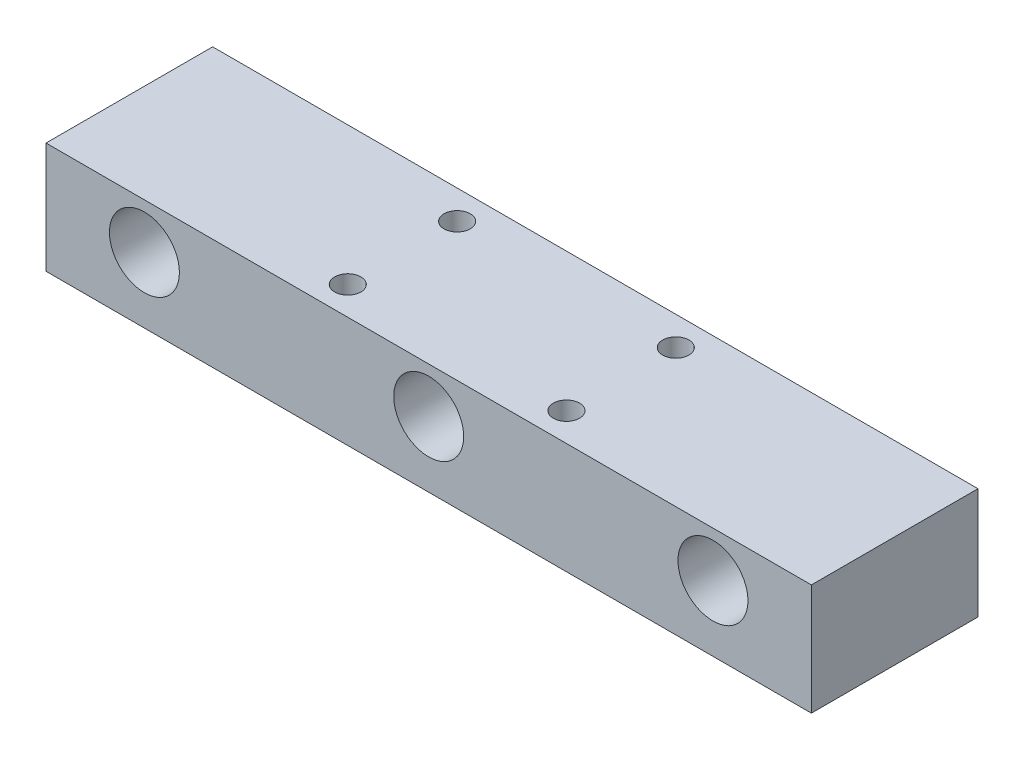
SolidWorks part; units mm, degrees
ref_plane "Front Plane" through (0, 0, 0) normal (0, 0, 1) x (1, 0, 0)
ref_plane "Top Plane" through (0, 0, 0) normal (0, 1, 0) x (1, 0, 0)
ref_plane "Right Plane" through (0, 0, 0) normal (1, 0, 0) x (0, 0, -1)
sketch "Sketch1" plane through (0, 0, 0) normal (0, 1, 0) x (1, 0, 0)
  line L1 (0, 0) -> (350, 0)
  line L2 (0, 0) -> (0, 76.2)
  line L3 (0, 76.2) -> (350, 76.2)
  line L4 (350, 0) -> (350, 76.2)
  dimension "D1" = 76.2
  dimension "D2" = 350
extrude "Boss-Extrude1" add sketch "Sketch1" along normal blind 50.8
sketch "Sketch3" plane through (0, 50.8, 0) normal (0, 1, 0) x (1, 0, 0)
  line L1 (0, 0) -> (175, 0)
  line L2 (0, 0) -> (0, 38)
  line L3 (0, 38) -> (175, 38)
  line L4 (175, 0) -> (175, 38)
  line L5 (125, 63) -> (225, 63)
  line L6 (125, 63) -> (125, 13)
  line L7 (125, 13) -> (225, 13)
  line L8 (225, 63) -> (225, 13)
  line L9 (125, 63) -> (225, 13) construction
  line L10 (125, 13) -> (225, 63) construction
  circle A0 centre (125, 63) radius 6
  circle A1 centre (125, 13) radius 6
  circle A2 centre (225, 63) radius 6
  circle A3 centre (225, 13) radius 6
  dimension "D1" = 175
  dimension "D2" = 38
  dimension "D3" = 100
  dimension "D4" = 50
extrude "Cut-Extrude2" cut sketch "Sketch3" against normal blind 50.8 contours A2 | A1 | A3 | A0
sketch "Sketch5" plane through (0, 0, 0) normal (0, 0, 1) x (1, 0, 0)
  line L0 (175, 30) -> (305, 30)
  line L1 (0, 0) -> (175, 0)
  line L2 (0, 0) -> (0, 30)
  line L4 (175, 0) -> (175, 30)
  line L5 (175, 30) -> (45, 30)
  circle A0 centre (175, 30) radius 16
  circle A1 centre (45, 30) radius 16
  circle A2 centre (305, 30) radius 16
  dimension "D3" = 130
  dimension "D1" = 30
  dimension "D2" = 175
  dimension "D4" = 130
extrude "Cut-Extrude3" cut sketch "Sketch5" against normal through all contours A1 | L0 A0 L5 | L4 A0 L0 | L5 A0 L4 | A2 region at (175, 36.7906, 0) region at (181.7906, 23.2094, 0) region at (168.2094, 23.2094, 0) region at (305, 45.5475, 0) region at (29.4525, 30, 0)
